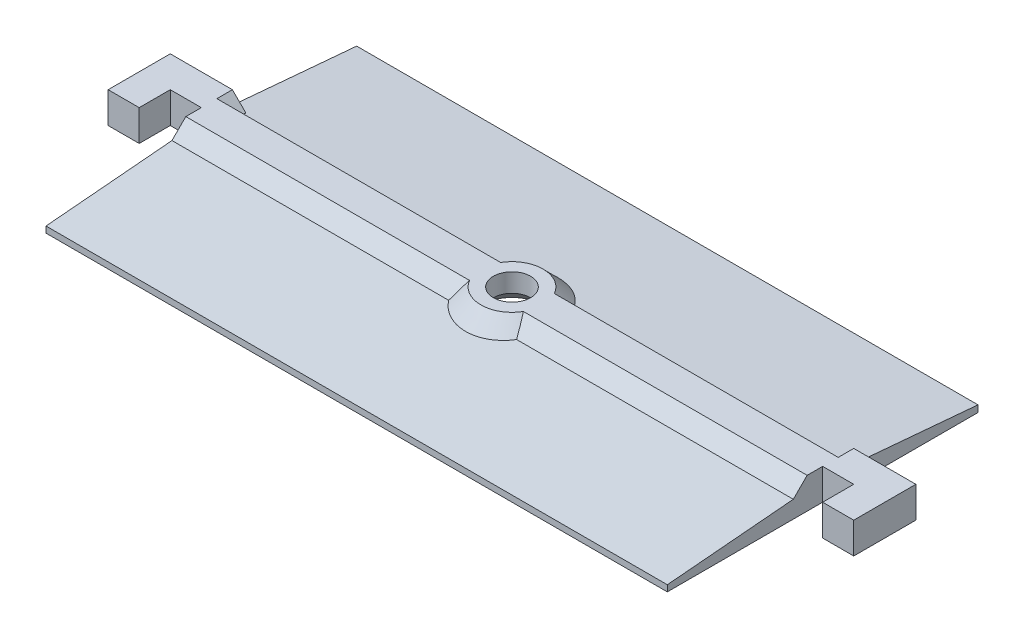
SolidWorks part; units mm, degrees
ref_plane "Płaszczyzna przednia" through (0, 0, 0) normal (0, 0, 1) x (1, 0, 0)
ref_plane "Płaszczyzna górna" through (0, 0, 0) normal (0, 1, 0) x (1, 0, 0)
ref_plane "Płaszczyzna prawa" through (0, 0, 0) normal (1, 0, 0) x (0, 0, -1)
sketch "Szkic1" plane through (0, 0, 0) normal (0, 1, 0) x (1, 0, 0)
  line L0 (-67.1429, 0) -> (64.2857, 0) construction
  line L1 (-50, -25) -> (50, -25)
  line L2 (-50, -25) -> (-50, 25)
  line L3 (-50, 25) -> (50, 25)
  line L4 (50, -25) -> (50, 25)
  line L5 (-50, -25) -> (50, 25) construction
  line L6 (-50, 25) -> (50, -25) construction
  line L7 (0, 36.1429) -> (0, -39) construction
  line L8 (-50, 0) -> (-55, 0)
  line L9 (-55, 0) -> (-55, -5)
  line L10 (-55, -5) -> (-60, -5)
  line L11 (-60, -5) -> (-60, 5)
  line L12 (-60, 5) -> (-50, 5)
  line L13 (-50, 2.5) -> (-4.3301, 2.5)
  line L14 (-50, -2.5) -> (-4.3301, -2.5)
  line L15 (4.3301, 2.5) -> (50, 2.5)
  line L16 (4.3301, -2.5) -> (50, -2.5)
  line L17 (60, 5) -> (50, 5)
  line L18 (50, 0) -> (55, 0)
  line L19 (60, -5) -> (60, 5)
  line L20 (55, -5) -> (60, -5)
  line L21 (55, 0) -> (55, -5)
  circle A0 centre (0, 0) radius 5
  circle A1 centre (0, 0) radius 3
  point P0 (0, 0)
  point P12 (-55, -2.5)
  point P22 (0, -2.5)
  point P23 (0, 2.5)
  dimension "D1" = 100
  dimension "D2" = 50
  dimension "D3" = 10
  dimension "D4" = 5
  dimension "D5" = 10
  dimension "D6" = 5
  dimension "D7" = 2.5
extrude "Dodanie-wyciągnięcie1" add sketch "Szkic1" along normal blind 3 contours A0 L14 L2 L1 L4 L16 | A0 L15 L4 L3 L2 L13 region at (0, 0, 13.8203) region at (0, 0, -13.8203)
extrude "Dodanie-wyciągnięcie2" add sketch "Szkic1<3>" along normal blind 5 contours L18 L21 L20 L19 L17 L4 | A0 L16 L4 L15 | A0 L13 L2 L14 | L12 L11 L10 L9 L8 L2 | A1 | A0 region at (-27.3911, 0, 0) region at (27.3911, 0, 0) region at (-55.8333, 0, -0.8333) region at (55.8333, 0, -0.8333) region at (0, 0, 0)
sketch "Szkic1<3>" plane through (0, 0, 0) normal (0, 1, 0) x (1, 0, 0) same geometry as "Szkic1"
chamfer "Sfazowanie1" distance 2 angle 45 8 edges at (-50, 3, -3.75) (50, 3, -3.75) (27.1651, 3, -2.5) (0, 3, -5) (-27.1651, 3, -2.5) (27.1651, 3, 2.5) (0, 3, 5) (-27.1651, 3, 2.5)
chamfer "Sfazowanie2" distance 22 angle 5 1 edges at (0, 3, -25) first distance on face at (0, 3, -9.05)
chamfer "Sfazowanie3" distance 2 angle 85 1 edges at (0, 3, 25) first distance on face at (0, 1.5, 25)
chamfer "Sfazowanie4" distance 2 angle 45 1 edges at (0, 0, 3)
